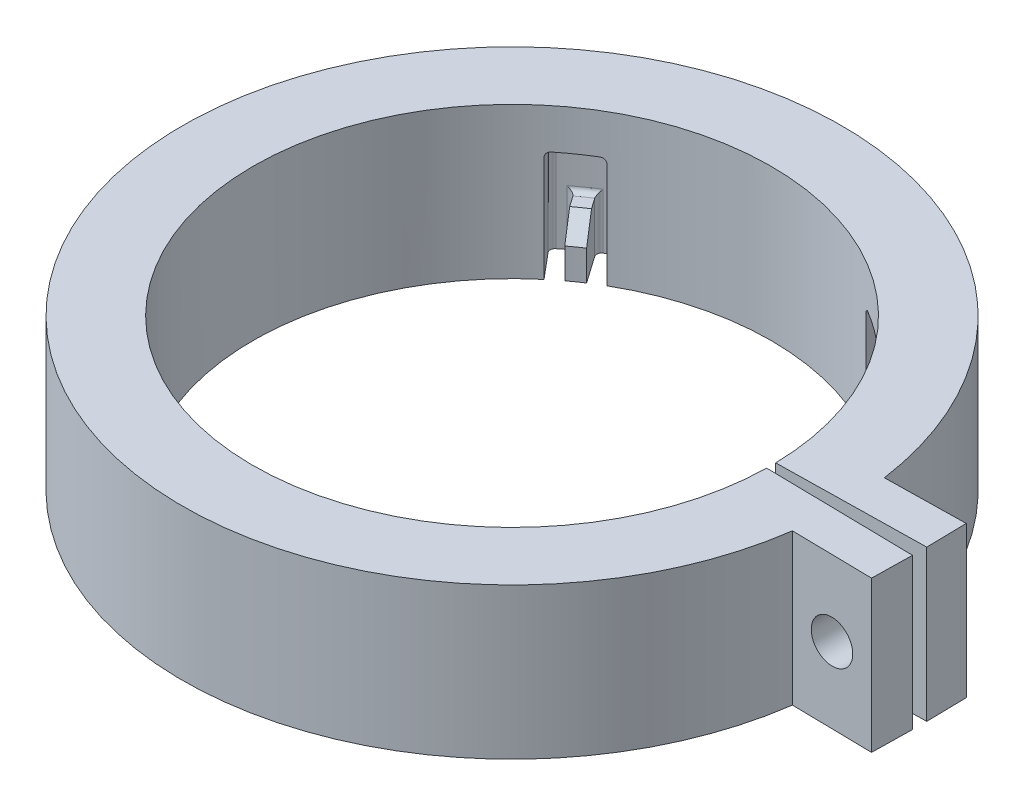
SolidWorks part; units mm, degrees
ref_plane "Front Plane" through (0, 0, 0) normal (0, 0, 1) x (1, 0, 0)
ref_plane "Top Plane" through (0, 0, 0) normal (0, 1, 0) x (1, 0, 0)
ref_plane "Right Plane" through (0, 0, 0) normal (1, 0, 0) x (0, 0, -1)
sketch "Sketch1" plane through (0, 0, 0) normal (0, 1, 0) x (1, 0, 0)
  line L0 (16.215, 2.2833) -> (20.2144, 2.3531)
  line L1 (20.2144, 2.3531) -> (20.2493, 0.3535)
  line L2 (20.2493, 0.3535) -> (16.3725, 0.2858)
  line L3 (16.3725, 0.2858) -> (12.873, 0.2247)
  line L4 (0, 0) -> (20.1482, 0) construction
  line L5 (16.3647, 0.7349) -> (16.4343, -3.252) construction
  line L6 (16.3725, -0.2858) -> (12.873, -0.2247)
  line L7 (20.2493, -0.3535) -> (16.3725, -0.2858)
  line L8 (16.215, -2.2833) -> (20.2144, -2.3531)
  line L9 (20.2144, -2.3531) -> (20.2493, -0.3535)
  circle A0 centre (0, 0) radius 12.875 construction
  circle A1 centre (0, 0) radius 16.375 construction
  arc A2 (16.215, 2.2833) -> (16.215, -2.2833) centre (0, 0) ccw
  arc A3 (12.873, 0.2247) -> (12.873, -0.2247) centre (0, 0) ccw
  dimension "D1" = 25.75
  dimension "D2" = 32.75
  dimension "D3" = 1
  dimension "D4" = 4
  dimension "D5" = 2
extrude "Boss-Extrude1" add sketch "Sketch1" along normal blind 7.5
sketch "Sketch2" plane through (-0.0349, 0, 1.9997) normal (-0.0175, 0, 0.9998) x (0.9998, 0, 0.0175)
  line L0 (16.2524, 7.5) -> (20.2524, 7.5) construction
  line L1 (18.2524, 7.5) -> (18.2524, 0) construction
  line L2 (16.2524, 0) -> (20.2524, 0) construction
  circle A0 centre (18.2524, 3.75) radius 1.05
  dimension "D1" = 2.1
extrude "Cut-Extrude1" cut sketch "Sketch2" against normal up to surface (2 mm away) up to face at (16.5612, 3.75, 0.2891)
sketch "Sketch3" plane through (-0.0349, 0, -1.9997) normal (-0.0175, 0, -0.9998) x (-0.9998, 0, 0.0175)
  line L0 (-18.2524, 7.5) -> (-18.2524, 0) construction
  line L1 (-20.2524, 7.5) -> (-16.2524, 7.5) construction
  line L2 (-20.2524, 0) -> (-16.2524, 0) construction
  circle A0 centre (-18.2524, 3.75) radius 1.05
  dimension "D1" = 2.1
extrude "Cut-Extrude2" cut sketch "Sketch3" against normal up to surface (2 mm away) up to face at (16.5612, 3.75, -0.2891)
sketch "Sketch4" plane through (0, 0, 0) normal (0, -1, 0) x (1, 0, 0)
  line L0 (2.2357, 12.6794) -> (2.3451, 13.2998) construction
  line L1 (7.2228, 10.6582) -> (7.5762, 11.1797) construction
  line L2 (-6.1595, 14.1597) -> (-11.0003, 15.0133) construction
  line L3 (8.08, 10.0773) -> (8.8675, 9.5436) construction
  line L4 (0, 0) -> (0, 14.0971) construction
  line L5 (-2.2357, 12.6794) -> (-2.3451, 13.2998) construction
  line L6 (-7.2228, 10.6582) -> (-7.5762, 11.1797) construction
  line L7 (-12.3866, -6.4135) -> (-4.1652, -13.3121) construction
  line L8 (-11.068, -8.4767) -> (-1.807, -13.8235) construction
  line L9 (-8.2759, -9.8628) -> (-9.4972, -11.3183)
  line L10 (-6.4375, -11.1501) -> (-7.3875, -12.7955)
  line L11 (8.2759, -9.8628) -> (9.4972, -11.3183)
  line L12 (6.4375, -11.1501) -> (7.3875, -12.7955)
  line L14 (-2.625, 13.1046) -> (2.625, 13.1046)
  line L15 (-2.625, 13.1046) -> (-2.625, 12.6046)
  line L16 (-2.625, 12.6046) -> (2.625, 12.6046)
  line L17 (2.625, 13.1046) -> (2.625, 12.6046)
  arc A0 (12.873, 0.2247) -> (12.873, -0.2247) centre (0, 0) ccw construction
  arc A1 (2.3451, 13.2998) -> (7.5762, 11.1797) centre (0, 0) cw construction
  arc A2 (2.2357, 12.6794) -> (7.2228, 10.6582) centre (0, 0) cw construction
  arc A3 (-2.3451, 13.2998) -> (-7.5762, 11.1797) centre (0, 0) ccw construction
  arc A4 (-2.2357, 12.6794) -> (-7.2228, 10.6582) centre (0, 0) ccw construction
  arc A5 (-9.4972, -11.3183) -> (-7.3875, -12.7955) centre (0, 0) ccw
  arc A6 (-8.2759, -9.8628) -> (-6.4375, -11.1501) centre (0, 0) ccw
  arc A7 (9.4972, -11.3183) -> (7.3875, -12.7955) centre (0, 0) cw
  arc A8 (8.2759, -9.8628) -> (6.4375, -11.1501) centre (0, 0) cw
  point P29 (-8.2759, -9.8628)
  point P31 (-6.4375, -11.1501)
  point P40 (0, 12.6046)
  dimension "D1" = 0.63
  dimension "D2" = 24.125
  dimension "D3" = 10
  dimension "D4" = 1.9
  dimension "D5" = 10
  dimension "D6" = 30
  dimension "D7" = 0.5
  dimension "D8" = 5.25
extrude "Cut-Extrude3" cut sketch "Sketch4" against normal blind 5.5
sketch "Sketch5" plane through (0, 0, 0) normal (0, -1, 0) x (1, 0, 0)
  line L2 (0, 0) -> (0, -3.7115) construction
  line L5 (-0.75, 13.1046) -> (-0.75, 12.8531) construction
  line L6 (2.625, 13.1046) -> (-2.625, 13.1046) construction
  line L7 (-8.4746, -12.103) -> (0, 0) construction
  line L8 (8.1529, -12.322) -> (7.0626, -10.765)
  line L9 (-8.7904, -11.8755) -> (-7.7002, -10.3185)
  line L10 (-8.1529, -12.322) -> (-7.0626, -10.765)
  line L11 (8.7904, -11.8755) -> (7.7002, -10.3185)
  line L12 (0.75, 13.1046) -> (0.75, 12.8531) construction
  line L13 (-0.75, 13.1046) -> (0.75, 13.1046) construction
  arc A0 (-9.4972, -11.3183) -> (-7.3875, -12.7955) centre (0, 0) ccw construction
  arc A1 (-8.2759, -9.8628) -> (-6.4375, -11.1501) centre (0, 0) ccw construction
  arc A2 (-8.7904, -11.8755) -> (-8.1529, -12.322) centre (0, 0) ccw
  arc A6 (2.625, 12.6046) -> (-2.625, 12.6046) centre (0, 0) ccw construction
  arc A7 (-7.0626, -10.765) -> (-7.7002, -10.3185) centre (0, 0) cw
  arc A8 (8.7904, -11.8755) -> (8.1529, -12.322) centre (0, 0) cw
  arc A9 (7.0626, -10.765) -> (7.7002, -10.3185) centre (0, 0) ccw
  arc A10 (-0.75, 12.8531) -> (0.75, 12.8531) centre (0, 0) cw construction
  dimension "D1" = 0.9
  dimension "D2" = 0.75
extrude "Boss-Extrude2" add sketch "Sketch5" against normal blind 2.5
fillet "Fillet1" radius 0.25 18 edges at (2.625, 2.75, 13.1046) (-2.625, 2.75, 13.1046) (2.625, 5.5, 12.8546) (-2.625, 5.5, 12.8546) (-7.3875, 2.75, -12.7955) (-9.4972, 2.75, -11.3183) (9.4972, 2.75, -11.3183) (7.3875, 2.75, -12.7955) (8.1529, 1.25, -12.322) (8.7904, 1.25, -11.8755) (-8.1529, 1.25, -12.322) (-8.7904, 1.25, -11.8755) (-8.8865, 5.5, -10.5906) (-6.9125, 5.5, -11.9728) (6.9125, 5.5, -11.9728) (8.8865, 5.5, -10.5906) (8.4746, 2.5, -12.103) (-8.4746, 2.5, -12.103)
chamfer "Chamfer1" distance 1 angle 45 2 edges at (-7.3848, 2.5, -10.5466) (7.3848, 2.5, -10.5466)
equation "\"24.12454degr\"=0.949785"
